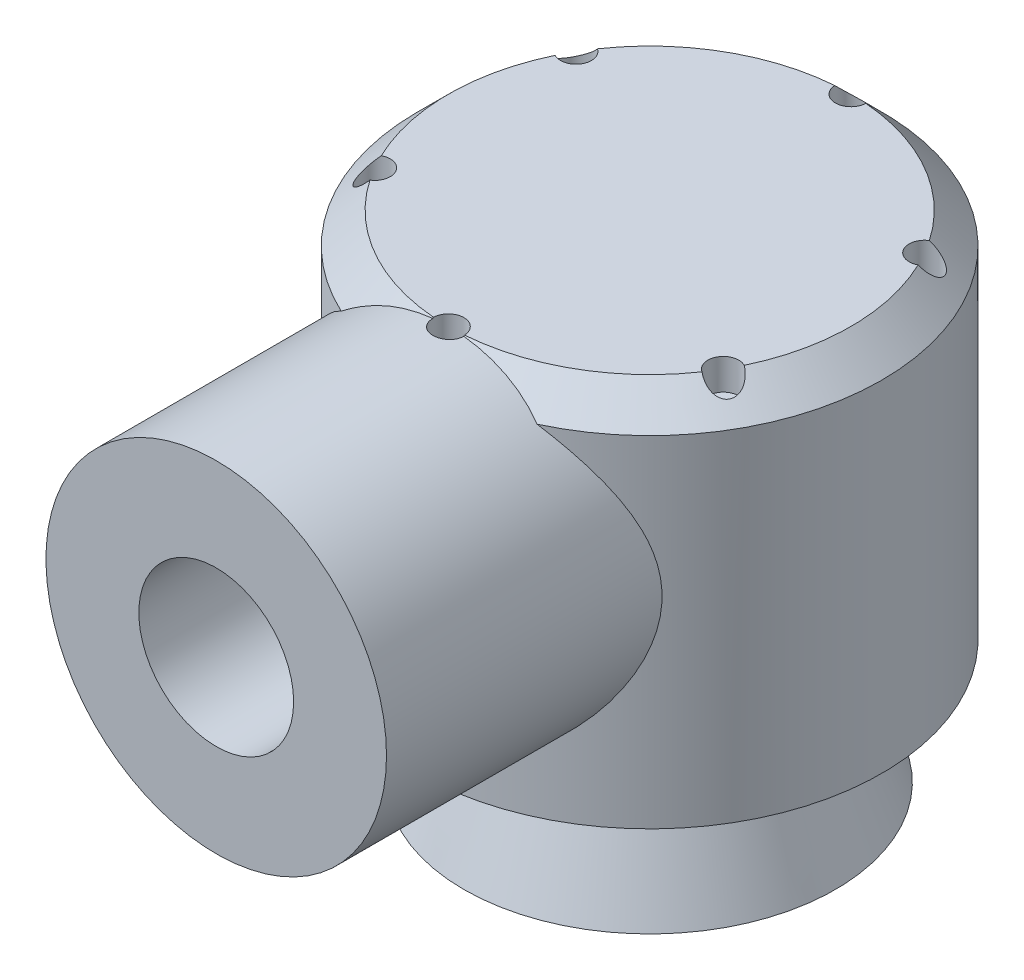
SolidWorks part; units mm, degrees
ref_plane "Front Plane" through (0, 0, 0) normal (0, 0, 1) x (1, 0, 0)
ref_plane "Top Plane" through (0, 0, 0) normal (0, 1, 0) x (1, 0, 0)
ref_plane "Right Plane" through (0, 0, 0) normal (1, 0, 0) x (0, 0, -1)
sketch "Sketch1" plane through (0, 0, 0) normal (0, 1, 0) x (1, 0, 0)
  circle A0 centre (0, 0) radius 152.4
  dimension "D1" = 304.8
extrude "Boss-Extrude1" add sketch "Sketch1" along normal blind 101.6 draft 20
sketch "Sketch2" plane through (0, 101.6, 0) normal (0, 1, 0) x (1, 0, 0)
  circle A0 centre (0, 0) radius 190.5
  dimension "D1" = 381
extrude "Boss-Extrude2" add sketch "Sketch2" along normal blind 50.8
sketch "Sketch3" plane through (0, 0, 0) normal (0, 0, 1) x (1, 0, 0)
  line L0 (0, 152.4) -> (0, 381)
  line L1 (190.5, 152.4) -> (-190.5, 152.4) construction
  circle A0 centre (0, 266.7) radius 139.7
  dimension "D2" = 279.4
  dimension "D1" = 228.6
sketch "Sketch4" plane through (0, 152.4, 0) normal (0, 1, 0) x (1, 0, 0)
  circle A1 centre (0, 0) radius 190.5
  circle A2 centre (0, 0) radius 190.5
  dimension "D1" = 0
extrude "Boss-Extrude3" add sketch "Sketch4" along normal blind 254
extrude "Boss-Extrude4" add sketch "Sketch3" along normal blind 355.6 contours A0 region at (-135.7487, 266.7, 0)
sketch "Sketch5" plane through (0, 0, 355.6) normal (0, 0, 1) x (1, 0, 0)
  circle A0 centre (0, 266.7) radius 63.5
  circle A1 centre (0, 266.7) radius 139.7 construction
  dimension "D2" = 127
  dimension "D1" = 76.2
extrude "Cut-Extrude1" cut sketch "Sketch5" against normal blind 127
chamfer "Chamfer1" distance 25.4 angle 45 1 edges at (0, 406.4, 190.5)
sketch "Sketch6" plane through (0, 406.4, 0) normal (0, 1, 0) x (1, 0, 0)
  circle A0 centre (0, 165.1) radius 12.7
  circle A1 centre (0, 0) radius 165.1 construction
  circle A2 centre (142.9808, 82.55) radius 12.7
  circle A3 centre (142.9808, -82.55) radius 12.7
  circle A4 centre (0, -165.1) radius 12.7
  circle A5 centre (-142.9808, -82.55) radius 12.7
  circle A6 centre (-142.9808, 82.55) radius 12.7
  point P17 (0, 0)
  dimension "D1" = 25.4
  dimension "D2" = 6
extrude "Cut-Extrude2" cut sketch "Sketch6" against normal blind 25.4
